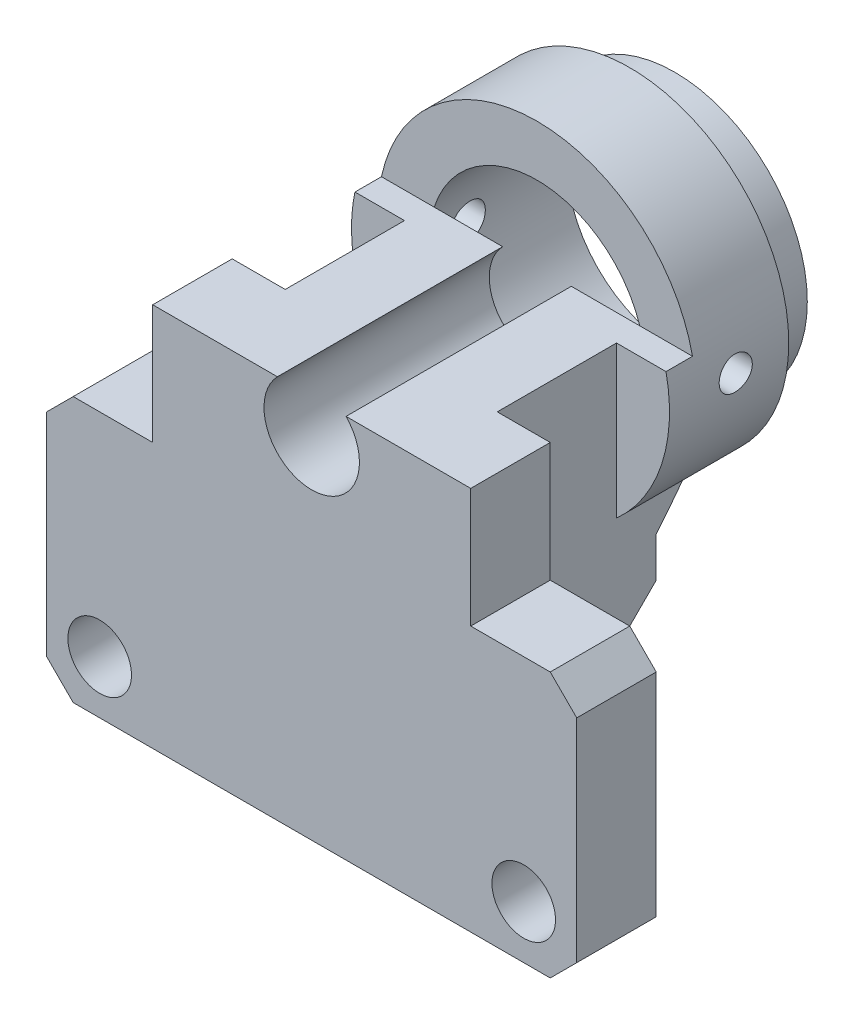
SolidWorks part; units mm, degrees
material "ABS"
ref_plane "Front Plane" through (0, 0, 0) normal (0, 0, 1) x (1, 0, 0)
ref_plane "Top Plane" through (0, 0, 0) normal (0, 1, 0) x (1, 0, 0)
ref_plane "Right Plane" through (0, 0, 0) normal (1, 0, 0) x (0, 0, -1)
sketch "Sketch1" plane through (0, 0, 0) normal (0, 0, 1) x (1, 0, 0)
  line L0 (0, 78.4471) -> (0, -76.9705) construction
  line L1 (-83.0616, 0) -> (77.155, 0) construction
  line L3 (-10, 5) -> (10, 5)
  line L4 (-10, 5) -> (-10, -5)
  line L5 (-10, -5) -> (10, -5)
  line L6 (10, 5) -> (10, -5)
  dimension "D1" = 20
  dimension "D2" = 10
extrude "Boss-Extrude1" add sketch "Sketch1" along normal blind 3
sketch "Sketch2" plane through (0, 0, 0) normal (0, 0, -1) x (-1, 0, 0)
  line L0 (0, -15.2672) -> (0, 42.8631) construction
  line L1 (4, 0) -> (-4, 0)
  line L2 (4, 0) -> (4, 9.5)
  line L3 (4, 9.5) -> (-4, 9.5)
  line L4 (-4, 0) -> (-4, 9.5)
  line L5 (-10, 5) -> (10, 5) construction
  dimension "D1" = 8
  dimension "D2" = 4.5
extrude "Boss-Extrude2" add sketch "Sketch2" along normal blind 6
sketch "Sketch3" plane through (0, 0, -6) normal (0, 0, -1) x (-1, 0, 0)
  line L0 (-4, 0) -> (4, 0) construction
  circle A0 centre (0, 8.25) radius 6
  dimension "D1" = 12
  dimension "D2" = 8.25
extrude "Boss-Extrude3" add sketch "Sketch3" along normal blind 6 and the other way blind 1.5
chamfer "Chamfer1" distance 1 angle 45 4 edges at (-10, 5, 1.5) (10, 5, 1.5) (10, -5, 1.5) (-10, -5, 1.5)
chamfer "Chamfer2" distance 1 angle 45 4 edges at (0, 0, -6) (0, 0, 0) (4, 2.5, 0) (-4, 2.5, 0)
chamfer "Chamfer3" distance 1 angle 45 1 edges at (0, 2.25, -6)
chamfer "Chamfer4" distance 2 angle 45 1 edges at (0, 5, 0)
chamfer "Chamfer5" distance 2 angle 45 2 edges at (4, 5, 0.5) (-4, 5, 0.5)
hole_wizard "M2 Clearance Hole1" positions "Sketch9" profile "Sketch10" hole size "M2" standard "ISO" end condition through all
sketch "Sketch9" plane through (0, 0, 0) normal (0, 0, -1) x (-1, 0, 0)
  line L0 (0, 17.4642) -> (0, -12.0288) construction
  line L2 (-18.4305, -3) -> (19.5599, -3) construction
  line L4 (10, 4) -> (10, -4) construction
  line L5 (9, -5) -> (-9, -5) construction
  point P0 (8, -3)
  point P2 (-8, -3)
  dimension "D1" = 2
  dimension "D2" = 2
sketch "Sketch10" plane through (-8, -3, 0) normal (1, 0, 0) x (0, 1, 0)
  line L0 (0, 0) -> (0, 3)
  line L1 (0, 3) -> (1.2, 3)
  line L2 (1.2, 3) -> (1.2, 0)
  line L5 (1.2, 0) -> (0, 0)
  line L11 (0, -6.35) -> (0, 107.95) construction
  dimension "Thru Hole Dia." = 2.4
  dimension "Thru Hole Depth" = 3
sketch "Sketch20" plane through (0, 0, -12) normal (0, 0, -1) x (-1, 0, 0)
  circle A0 centre (0, 8.25) radius 6
  circle A1 centre (0, 8.25) radius 6 construction
  circle A2 centre (0, 8.25) radius 4
  dimension "D1" = 8
extrude "Cut-Extrude9" [suppressed] cut sketch "Sketch20" against normal blind 3
sketch "Sketch21" plane through (0, 0, -12) normal (0, 0, -1) x (-1, 0, 0)
  circle A0 centre (0, 8.25) radius 4.075
  point P4 (0, 8.25)
  dimension "D1" = 8.15
extrude "Cut-Extrude10" cut sketch "Sketch21" against normal offset from surface (6.5 mm away) 1 contours A0 up to face at (0, 9.257, -4.5)
ref_plane "Plane3" through (0, 0, -5.5) normal (0, 0, -1) x (-1, 0, 0)
sketch "Sketch22" [suppressed] plane through (0, 0, -5.5) normal (0, 0, -1) x (-1, 0, 0)
  line L0 (0, 12.75) -> (0, 11.6583) construction
  line L1 (1, 11.6583) -> (-1, 11.6583)
  line L2 (-1, 11.6583) -> (-1, 13.6583)
  line L3 (1, 11.6583) -> (1, 13.6583)
  circle A0 centre (0, 8.25) radius 5.5 construction
  arc A1 (1, 13.6583) -> (-1, 13.6583) centre (0, 8.25) ccw
  dimension "D1" = 2
  dimension "D2" = 1
extrude "Cut-Extrude11" [suppressed] cut sketch "Sketch22" against normal through all and the other way through all
ref_plane "Plane4" through (0, 0, 0) normal (0, 0, 1) x (1, 0, 0)
sketch "Sketch25" plane through (0, 0, 0) normal (0, 0, 1) x (1, 0, 0)
  line L1 (-6, 9.5) -> (6, 9.5)
  line L2 (-6, 9.5) -> (-6, 5)
  line L3 (-6, 5) -> (6, 5)
  line L4 (6, 9.5) -> (6, 5)
extrude "Boss-Extrude6" add sketch "Sketch25" along normal up to surface (3 mm away) up to face at (-9.2, -3, 3)
hole_wizard "CSK SLOT for M1.6 Countersunk Flat Head Screw2" positions "Sketch23" profile "Sketch24" size "M1.6" standard "ISO" slot yes
sketch "Sketch23" plane through (0, 0, 3) normal (0, 0, 1) x (1, 0, 0)
  point P2 (0, 8.25)
sketch "Sketch24" plane through (0, 8.25, 3) normal (1, 0, 0) x (0, -1, 0)
  line L0 (0, 0) -> (0, 40.5408)
  line L1 (0, 40.5408) -> (0.9, 40)
  line L2 (0.9, 40) -> (0.9, 9.9)
  line L3 (0.9, 9.9) -> (1.8, 9)
  line L4 (1.8, 9) -> (1.8, 0)
  line L6 (1.8, 0) -> (0, 0)
  line L7 (-0.9, 9.9) -> (-1.8, 9) construction
  line L10 (0, 40.5408) -> (-0.9, 40) construction
  line L11 (0, -6.35) -> (0, 107.95) construction
  dimension "Hole Dia." = 1.8
  dimension "Hole Depth" = 40
  dimension "C'Sink Dia." = 3.6
  dimension "C'Sink Angle" = 90
  dimension "Drill Angle" = 118
  dimension "Head Clearance" = 9
sketch "Sketch26" plane through (0, 0, -5.5) normal (0, 0, -1) x (-1, 0, 0)
  circle A2 centre (0, 8.25) radius 1
  dimension "D1" = 2
extrude "Cut-Extrude12" [suppressed] cut sketch "Sketch26" against normal through all
sketch "Sketch27" [suppressed] plane through (0, 0, 3) normal (0, 0, 1) x (1, 0, 0)
  line L0 (-4.5, 8.25) -> (4.5, 8.25)
  circle A0 centre (0, 8.25) radius 4.5
hole_wizard "CSK SLOT for M1.6 Countersunk Flat Head Screw3" [suppressed] positions "Sketch30" profile "Sketch31" size "M1.6" standard "ISO"
sketch "Sketch30" [suppressed] plane through (0, 0, 3) normal (0, 0, 1) x (1, 0, 0)
  line L0 (-4.5, 8.25) -> (4.5, 8.25) construction
  point P0 (-3, 8.25)
  point P4 (3, 8.25)
  dimension "D1" = 1.5
  dimension "D2" = 1.5
sketch "Sketch31" plane through (-3, 8.25, 3) normal (1, 0, 0) x (0, -1, 0)
  line L0 (0, 0) -> (0, 13.5)
  line L1 (0, 13.5) -> (0.9, 13.5)
  line L2 (0.9, 13.5) -> (0.9, 9.9)
  line L3 (0.9, 9.9) -> (1.8, 9)
  line L4 (1.8, 9) -> (1.8, 0)
  line L6 (1.8, 0) -> (0, 0)
  line L7 (-0.9, 9.9) -> (-1.8, 9) construction
  line L11 (0, -6.35) -> (0, 107.95) construction
  dimension "Thru Hole Dia." = 1.8
  dimension "Thru Hole Depth" = 13.5
  dimension "C'Sink Dia." = 3.6
  dimension "C'Sink Angle" = 90
  dimension "Head Clearance" = 9
ref_plane "Plane5" through (-6, 0, 0) normal (-1, 0, 0) x (0, 0, 1)
hole_wizard "M1.6 Tapped Hole2" positions "Sketch36" profile "Sketch37" tap size "M1.6" standard "ISO" end condition through all
sketch "Sketch36" plane through (-6, 0, 0) normal (-1, 0, 0) x (0, 0, 1)
  line L0 (-8.46, 8.25) -> (-4.5, 8.25)
  line L2 (-4.5, 3.7779) -> (-4.5, 9.5) construction
  point P0 (-7, 8.25)
  dimension "D1" = 2.5
sketch "Sketch37" plane through (-6, 8.25, -7) normal (0, 1, 0) x (0, 0, 1)
  line L0 (0, 0) -> (0, 16)
  line L1 (0, 16) -> (0.625, 16)
  line L2 (0.625, 16) -> (0.625, 0)
  line L5 (0.625, 0) -> (0, 0)
  line L11 (0, -6.35) -> (0, 107.95) construction
  dimension "Thru Tap Drill Dia." = 1.25
  dimension "Thru Tap Drill Depth" = 16
cosmetic thread "Hole Thread4" parameters "D2"=1.6
sketch "Sketch38" plane through (0, 0, -4.5) normal (0, 0, 1) x (1, 0, 0)
  circle A0 centre (0, 8.25) radius 6
  arc A1 (4, 3.7779) -> (-4, 3.7779) centre (0, 8.25) ccw construction
extrude "Boss-Extrude7" [suppressed] add sketch "Sketch38" along normal blind 1
sketch "Sketch39" [suppressed] plane through (0, 0, -4.5) normal (0, 0, -1) x (-1, 0, 0)
  circle A0 centre (0, 8.25) radius 1.8
extrude "Cut-Extrude14" [suppressed] cut sketch "Sketch39" against normal through all
sketch "Sketch40" plane through (0, 0, -12) normal (0, 0, -1) x (-1, 0, 0)
  circle A0 centre (0, 8.25) radius 6
  circle A1 centre (0, 8.25) radius 6 construction
extrude "Cut-Extrude15" cut sketch "Sketch40" against normal blind 3
sketch "Sketch41" plane through (0, 0, -9) normal (0, 0, -1) x (-1, 0, 0)
  circle A0 centre (0, 8.25) radius 5
  circle A1 centre (0, 8.25) radius 4.075
  dimension "D1" = 10
extrude "Boss-Extrude8" add sketch "Sketch41" along normal blind 1.7
sketch "Sketch43" plane through (0, 0, -4.5) normal (0, 0, 1) x (1, 0, 0)
  line L0 (-1.2952, 9.5) -> (-5.8683, 9.5)
  line L1 (-5.8683, 9.5) -> (5.8683, 9.5)
  line L2 (6, 9.5) -> (1.2952, 9.5) construction
  arc A0 (5.8683, 9.5) -> (-5.8683, 9.5) centre (0, 8.25) ccw
  arc A1 (4, 3.7779) -> (-4, 3.7779) centre (0, 8.25) ccw construction
  line M2 (-4, 9.5) -> (-1.2952, 9.5)
  arc M3 (-1.2952, 9.5) -> (1.2952, 9.5) centre (0, 8.25) cw
  line M4 (1.2952, 9.5) -> (4, 9.5)
  arc M6 (4, 3.7779) -> (-4, 3.7779) centre (0, 8.25) ccw
extrude "Cut-Extrude16" cut sketch "Sketch43" against normal blind 1 contours L1 L0 M4 M6 M2 M3
